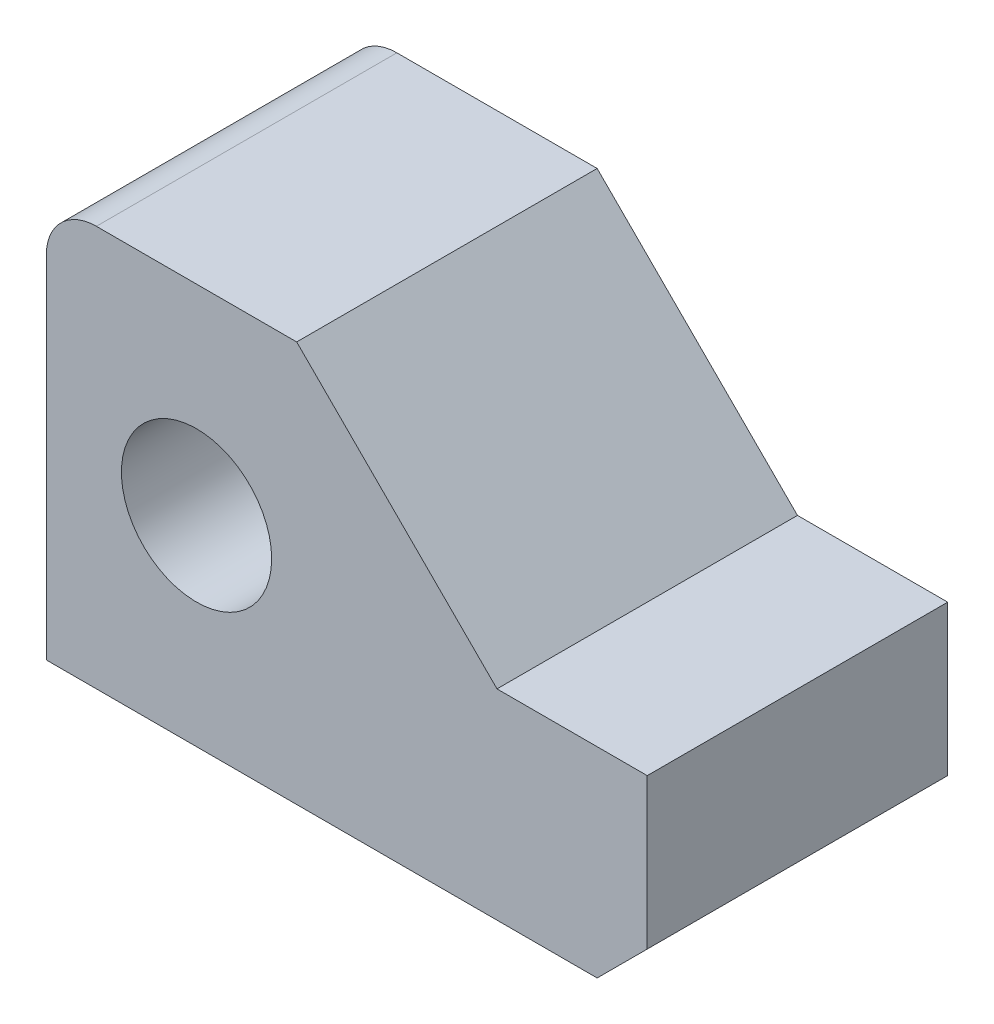
SolidWorks part; units mm, degrees
ref_plane "Front Plane" through (0, 0, 0) normal (0, 0, 1) x (1, 0, 0)
ref_plane "Top Plane" through (0, 0, 0) normal (0, 1, 0) x (1, 0, 0)
ref_plane "Right Plane" through (0, 0, 0) normal (1, 0, 0) x (0, 0, -1)
sketch "Sketch1" plane through (0, 0, 0) normal (0, 0, 1) x (1, 0, 0)
  line L0 (0, 0) -> (55, 0)
  line L1 (60, 5) -> (60, 20)
  line L2 (60, 20) -> (45, 20)
  line L3 (45, 20) -> (25, 40)
  line L4 (25, 40) -> (5, 40)
  line L5 (0, 35) -> (0, 0)
  line L6 (55, 0) -> (60, 5)
  circle A0 centre (15, 20) radius 7.5
  arc A1 (0, 35) -> (5, 40) centre (5, 35) cw
  point P1 (60, 0)
  point P11 (0, 40)
  dimension "D7" = 15
  dimension "D10" = 5
  dimension "D1" = 60
  dimension "D2" = 270
  dimension "D3" = 20
  dimension "D4" = 45
  dimension "D5" = 40
  dimension "D6" = 25
  dimension "D8" = 15
  dimension "D9" = 20
extrude "Boss-Extrude1" add sketch "Sketch1" along normal blind 15 and the other way blind 15
